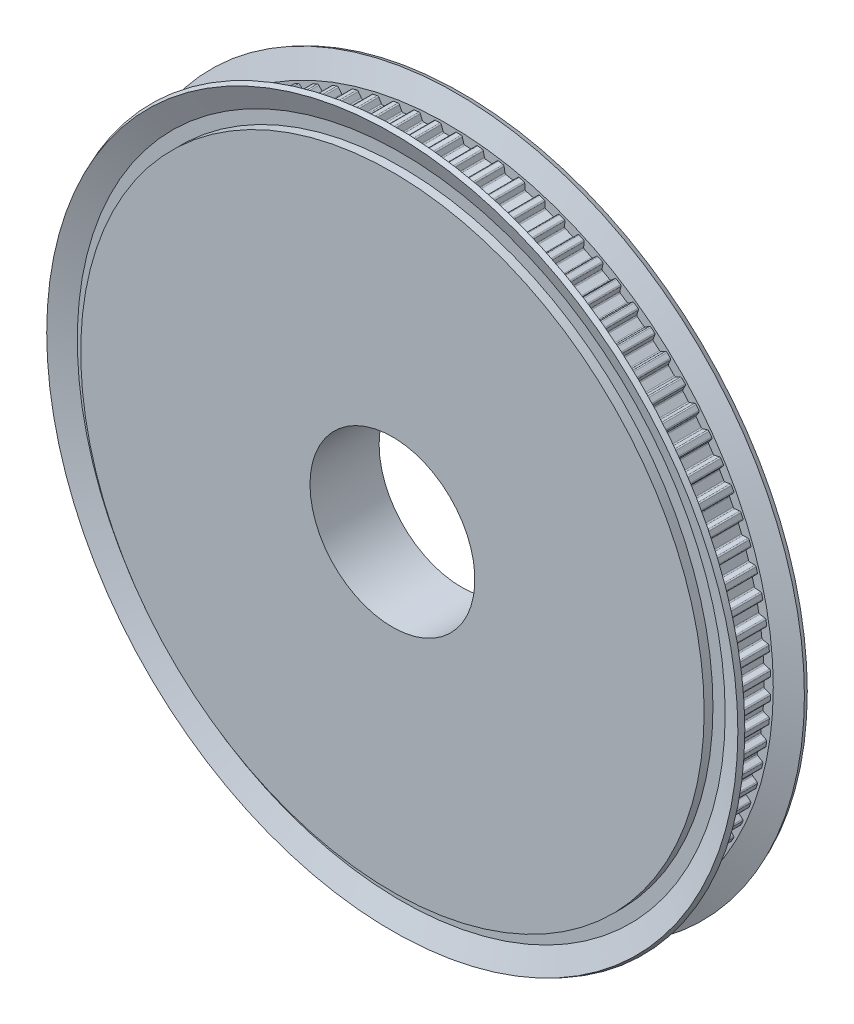
SolidWorks part; units mm, degrees
ref_plane "Front Plane" through (0, 0, 0) normal (0, 0, 1) x (1, 0, 0)
ref_plane "Top Plane" through (0, 0, 0) normal (0, 1, 0) x (1, 0, 0)
ref_plane "Right Plane" through (0, 0, 0) normal (1, 0, 0) x (0, 0, -1)
ref_axis "Axis1" through (0, 0, 55) along (0, 0, -1)
sketch "SketchRevolveGearBelt01" plane through (0, 0, 0) normal (1, 0, 0) x (0, 0, -1)
  line L0 (0, 0) -> (1, 0) construction
  line L1 (3.302, 0) -> (3.302, 29.7767)
  line L2 (3.302, 29.7767) -> (2.4606, 29.7767)
  line L3 (2.4606, 29.7767) -> (2.4606, 30.9456)
  line L4 (2.4606, 30.9456) -> (3.3162, 33.0113)
  line L5 (3.3162, 33.0113) -> (2.8469, 33.2057)
  line L6 (2.8469, 33.2057) -> (2.032, 31.0467)
  line L7 (2.032, 31.0467) -> (2.032, 30.7967)
  line L8 (2.032, 30.7967) -> (-2.032, 30.7967)
  line L9 (-2.032, 30.7967) -> (-2.032, 31.0467)
  line L10 (-2.032, 31.0467) -> (-2.8469, 33.2057)
  line L11 (-2.8469, 33.2057) -> (-3.3162, 33.0113)
  line L12 (-3.3162, 33.0113) -> (-2.4606, 30.9456)
  line L13 (-2.4606, 30.9456) -> (-2.4606, 29.7767)
  line L14 (-2.4606, 29.7767) -> (-3.302, 29.7767)
  line L15 (-3.302, 29.7767) -> (-3.302, 0)
  line L16 (-3.302, 0) -> (3.302, 0)
  dimension "GearBeltSide1" = 3.302
  dimension "GearBeltFlange1OutsideWidth" = 2.4606
  dimension "GearBeltFlange1OutsideLength" = 1.169
  dimension "GearBeltFlange1X" = 0.8556
  dimension "GearBeltFlange1Y" = 2.0656
  dimension "GearBeltFlangeThickness" = 1.821
  dimension "GearBeltToothWidth1" = 2.032
  dimension "GearBeltFlangeInside" = 0.25
  dimension "GearBeltOutsideDiameter" = 30.7967
  dimension "GearBeltToothWidth2" = 2.032
  dimension "GearBeltFlange2X" = 0.8556
  dimension "GearBeltFlange2OutsideWidth" = 2.4606
revolve "GearBelt01" add sketch "SketchRevolveGearBelt01" angle 360 about L0
sketch "SketchToothGearBelt01" plane through (0, 0, 0) normal (0, 0, 1) x (1, 0, 0)
  line L0 (-0.6657, 30.7031) -> (-0.499, 30.2452)
  line L1 (-0.3797, 30.1617) -> (0.3797, 30.1617)
  line L2 (0.499, 30.2452) -> (0.6657, 30.7031)
  line L3 (0.7883, 30.7866) -> (0, 33.3266)
  line L4 (0, 33.3266) -> (-0.7883, 30.7866)
  arc A0 (-0.7883, 30.7866) -> (-0.6657, 30.7031) centre (-0.785, 30.6596) cw
  arc A1 (-0.499, 30.2452) -> (-0.3797, 30.1617) centre (-0.3797, 30.2887) ccw
  arc A2 (0.3797, 30.1617) -> (0.499, 30.2452) centre (0.3797, 30.2887) ccw
  arc A3 (0.6657, 30.7031) -> (0.7883, 30.7866) centre (0.785, 30.6596) cw
  dimension "GearBeltToothR1" = 0.254
  dimension "GearBeltToothR2" = 0.254
  dimension "GearBeltToothX1" = 0.1666
  dimension "GearBeltToothY1" = 0.4578
  dimension "GearBeltToothRootX" = 30.1617
  dimension "GearBeltToothRootY" = 30.1617
  dimension "GearBeltToothX2" = 0.1666
  dimension "GearBeltToothY2" = 0.4578
  dimension "GearBeltToothCapX1" = 0.7883
  dimension "GearBeltToothCapY1" = 2.54
  dimension "GearBeltToothCapX2" = 0.7883
  dimension "GearBeltToothCapY2" = 2.54
extrude "ToothExtrudeCutGearBelt01" cut sketch "SketchToothGearBelt01" against normal blind 2.032 and the other way blind 2.032
pattern_circular "PatternGearBelt01" count 96 every 3.75 about axis through (0, 0, 55) along (0, 0, -1) of "ToothExtrudeCutGearBelt01"
sketch "BoreRevolveSketch" plane through (0, 0, 0) normal (1, 0, 0) x (0, 0, -1)
  line L0 (0, 0) -> (1, 0) construction
  line L1 (-3.302, 0) -> (3.302, 0)
  line L2 (3.302, 0) -> (3.302, 7.75)
  line L3 (3.302, 7.75) -> (-3.302, 7.75)
  line L4 (-3.302, 7.75) -> (-3.302, 0)
  dimension "BoreSide1" = 3.302
  dimension "TaperSide1" = 7.75
  dimension "BoreSide2" = 3.302
  dimension "TaperSide2" = 7.75
revolve "BoreRevolveCut" cut sketch "BoreRevolveSketch" angle 360 about L0
sketch "AuxiliarySketchGearBelt01" plane through (0, 0, 0) normal (0, 0, 1) x (1, 0, 0)
  circle A0 centre (0, 0) radius 31.0467 construction
  dimension "PitchDiameter" = 62.0933
sketch "Sketch1" plane through (0, 0, -3.302) normal (0, 0, -1) x (-1, 0, 0)
  circle A0 centre (0, 0) radius 7.875
  dimension "D1" = 15.75
extrude "Cut-Extrude1" cut sketch "Sketch1" against normal blind 10
